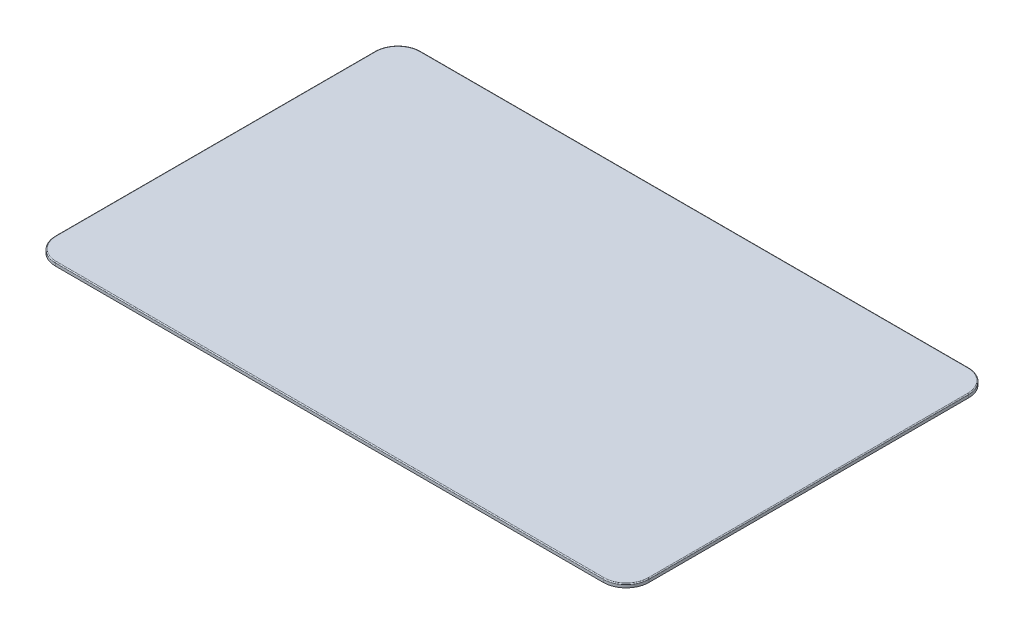
SolidWorks part; units mm, degrees
ref_plane "Спереди" through (0, 0, 0) normal (0, 0, 1) x (1, 0, 0)
ref_plane "Сверху" through (0, 0, 0) normal (0, 1, 0) x (1, 0, 0)
ref_plane "Справа" through (0, 0, 0) normal (1, 0, 0) x (0, 0, -1)
sketch "Эскиз1" plane through (0, 0, 0) normal (0, 1, 0) x (1, 0, 0)
  line L1 (-600, -400) -> (600, -400)
  line L2 (-650, -350) -> (-650, 350)
  line L3 (-600, 400) -> (600, 400)
  line L4 (650, -350) -> (650, 350)
  line L5 (-650, -400) -> (650, 400) construction
  line L6 (-650, 400) -> (650, -400) construction
  arc A0 (-600, 400) -> (-650, 350) centre (-600, 350) ccw
  arc A1 (600, 400) -> (650, 350) centre (600, 350) cw
  arc A2 (650, -350) -> (600, -400) centre (600, -350) cw
  arc A3 (-600, -400) -> (-650, -350) centre (-600, -350) cw
  point P0 (0, 0)
  dimension "D1" = 50
  dimension "D4" = 50
  dimension "D2" = 1300
  dimension "D3" = 800
extrude "Бобышка-Вытянуть1" add sketch "Эскиз1" along normal blind 8
fillet "Скругление1" radius 2 8 edges at (-635.3553, 8, -385.3553) (0, 8, -400) (635.3553, 8, -385.3553) (650, 8, 0) (635.3553, 8, 385.3553) (0, 8, 400) (-635.3553, 8, 385.3553) (-650, 8, 0)
sketch "Эскиз2" plane through (0, 0, 0) normal (0, -1, 0) x (1, 0, 0)
  line L0 (0, 398) -> (0, 197.3407) construction
  line L1 (-498, -35) -> (-405.9312, -35) construction
  line L2 (-494.82, 35) -> (-402.7512, 35) construction
  line L3 (-498, -100.1909) -> (-498, 80.8489) construction
  line L4 (-505.5, -118.7139) -> (-423, -118.7139)
  line L5 (-480.5, -93.7139) -> (-448, -93.7139)
  line L6 (-418, 113.7139) -> (-418, 29.5)
  line L7 (250, 398) -> (250, -398) construction
  line L8 (-250, 398) -> (-250, -398) construction
  line L9 (-648, 0) -> (648, 0) construction
  line L10 (302.5206, -212.9276) -> (307.7592, -212.906)
  line L11 (145, 35) -> (145, 50)
  line L12 (259.7408, -280.6043) -> (259.7408, -218.094)
  line L13 (262.2408, -283.1043) -> (308.0492, -283.1043)
  line L14 (265.5, -179.2861) -> (207.5, -179.2861)
  line L15 (-505.5, 118.7139) -> (-423, 118.7139)
  line L16 (-443, 88.7139) -> (-443, -88.7139)
  line L17 (-480.5, 93.7139) -> (-448, 93.7139)
  line L18 (-485.5, 84.9278) -> (-485.5, 88.7139)
  line L19 (-510.5, 85.0723) -> (-510.5, 113.7139)
  line L20 (-523.5388, 12.3957) -> (-523.2695, 77.6043)
  line L21 (403, -14.5) -> (302.5, -14.5)
  line L22 (403, 14.5) -> (302.5, 14.5)
  line L23 (418, -29.5) -> (418, -113.7139)
  line L24 (265.5, 174.2861) -> (207.5, 174.2861)
  line L25 (-515.5206, -80.0724) -> (-520.7592, -80.094)
  line L26 (22.5, -35) -> (-22.5, -35)
  line L27 (270.5, -174.2861) -> (270.5, 169.2861)
  line L28 (197.4794, 212.9276) -> (192.2408, 212.906)
  line L29 (240.2592, 280.6043) -> (240.2592, 218.125)
  line L30 (25, -32.5) -> (25, 35)
  line L31 (237.7592, 283.1043) -> (191.9508, 283.1043)
  line L32 (250, 213.1446) -> (245.2798, 213.1251)
  line L33 (310.5388, -280.6043) -> (310.2695, -215.3957)
  line L34 (-472.7408, -12.3957) -> (-472.7408, -77.3957)
  line L35 (297.5, -207.9277) -> (297.5, -19.5)
  line L36 (202.5, -207.9277) -> (202.5, -184.2861)
  line L37 (-475.2408, 79.906) -> (-480.5206, 79.9278)
  line L38 (-302.5206, 212.9276) -> (-307.7592, 212.906)
  line L39 (-265.5, 179.2861) -> (-207.5, 179.2861)
  line L40 (-259.7408, 280.6043) -> (-259.7408, 218.1043)
  line L41 (189.4612, -280.6043) -> (189.7305, -215.3957)
  line L42 (-262.2408, 283.1043) -> (-308.0492, 283.1043)
  line L43 (-254.7408, 213.1043) -> (-245.2592, 213.1043)
  line L44 (237.7592, -283.1043) -> (191.9508, -283.1043)
  line L45 (95, 100) -> (26, 100)
  line L46 (240.2592, -280.6043) -> (240.2592, -218.094)
  line L47 (197.4794, -212.9276) -> (192.2408, -212.906)
  line L48 (-25, -32.5) -> (-25, 35)
  line L50 (-310.5388, 280.6043) -> (-310.2695, 215.3957)
  line L51 (-297.5, 207.9277) -> (-297.5, 14.5)
  line L52 (-202.5, 207.9277) -> (-202.5, 184.2861)
  line L53 (-189.4612, 280.6043) -> (-189.7305, 215.3957)
  line L54 (-265.5, -174.2861) -> (-207.5, -174.2861)
  line L55 (-95, 100) -> (-23, 100)
  line L56 (-475.2408, -9.8957) -> (-521.0492, -9.8957)
  line L57 (-475.2408, -79.906) -> (-480.5206, -79.9278)
  line L58 (-475.2408, 9.8957) -> (-521.0492, 9.8957)
  line L59 (-523.5388, -12.3957) -> (-523.2695, -77.6043)
  line L60 (-510.5, -85.0723) -> (-510.5, -113.7139)
  line L61 (-472.7408, 12.3957) -> (-472.7408, 77.3957)
  line L62 (-515.5206, 80.0724) -> (-520.7592, 80.094)
  line L63 (-485.5, -84.9278) -> (-485.5, -88.7139)
  line L64 (-23, 147.3407) -> (-23.5, 147.3407)
  line L65 (-197.4794, -212.9276) -> (-192.2408, -212.906)
  line L66 (-240.2592, -280.6043) -> (-240.2592, -218.125)
  line L67 (82.5, -35) -> (37.5, -35)
  line L68 (-237.7592, -283.1043) -> (-191.9508, -283.1043)
  line L69 (-250, -213.1446) -> (-245.2798, -213.1251)
  line L70 (485.5, -84.9278) -> (485.5, -88.7139)
  line L71 (-189.4612, -280.6043) -> (-189.7305, -215.3957)
  line L72 (-202.5, -207.9277) -> (-202.5, -179.2861)
  line L73 (-297.5, -207.9277) -> (-297.5, -14.5)
  line L74 (515.5206, 80.0724) -> (520.7592, 80.094)
  line L75 (472.7408, 12.3957) -> (472.7408, 77.3957)
  line L76 (510.5, -85.0723) -> (510.5, -113.7139)
  line L77 (523.5388, -12.3957) -> (523.2695, -77.6043)
  line L78 (475.2408, 9.8957) -> (521.0492, 9.8957)
  line L79 (475.2408, -79.906) -> (480.5206, -79.9278)
  line L80 (475.2408, -9.8957) -> (521.0492, -9.8957)
  line L81 (85, -32.5) -> (85, 35)
  line L82 (35, -32.5) -> (35, 35)
  line L84 (-145, 35) -> (-145, 50)
  line L86 (142.5, -35) -> (97.5, -35)
  line L87 (145, -32.5) -> (145, 35)
  line L88 (95, -32.5) -> (95, 35)
  line L89 (21, 105) -> (21, 142.3407)
  line L90 (26.5, 149.8407) -> (26.5, 194.8407)
  line L91 (-18, 105) -> (-18, 142.3407)
  line L92 (-97.5, -35) -> (-142.5, -35)
  line L93 (-95, -32.5) -> (-95, 35)
  line L94 (-145, -32.5) -> (-145, 35)
  line L95 (24, 197.3407) -> (-21, 197.3407)
  line L96 (-23.5, 149.8407) -> (-23.5, 194.8407)
  line L98 (-37.5, -35) -> (-82.5, -35)
  line L99 (-35, -32.5) -> (-35, 35)
  line L100 (-85, -32.5) -> (-85, 35)
  line L105 (0, 147.3407) -> (0, 115.0711) construction
  line L108 (0, 0) -> (0, -400) construction
  line L112 (-310.5388, -280.6043) -> (-310.2695, -215.3957)
  line L114 (-237.7592, 283.1043) -> (-191.9508, 283.1043)
  line L116 (-240.2592, 280.6043) -> (-240.2592, 218.1043)
  line L117 (-197.4794, 212.9276) -> (-192.2408, 212.906)
  line L118 (-270.5, 174.2861) -> (-270.5, -169.2861)
  line L122 (-418, -29.5) -> (-418, -113.7139)
  line L123 (189.4612, 280.6043) -> (189.7305, 215.3957)
  line L124 (202.5, 207.9277) -> (202.5, 179.2861)
  line L125 (297.5, 207.9277) -> (297.5, 19.5)
  line L126 (310.5388, 280.6043) -> (310.2695, 215.3957)
  line L127 (250, 213.1446) -> (254.7202, 213.1251)
  line L128 (262.2408, 283.1043) -> (308.0492, 283.1043)
  line L129 (259.7408, 280.6043) -> (259.7408, 218.125)
  line L131 (302.5206, 212.9276) -> (307.7592, 212.906)
  line L132 (498, -100.1909) -> (498, 80.8489) construction
  line L133 (475.2408, 79.906) -> (480.5206, 79.9278)
  line L134 (472.7408, -12.3957) -> (472.7408, -77.3957)
  line L135 (515.5206, -80.0724) -> (520.7592, -80.094)
  line L136 (523.5388, 12.3957) -> (523.2695, 77.6043)
  line L137 (-403, 14.5) -> (-297.5, 14.5)
  line L138 (-403, -14.5) -> (-297.5, -14.5)
  line L139 (-250, -213.1446) -> (-254.7202, -213.1251)
  line L140 (510.5, 85.0723) -> (510.5, 113.7139)
  line L141 (485.5, 84.9278) -> (485.5, 88.7139)
  line L142 (-262.2408, -283.1043) -> (-308.0492, -283.1043)
  line L143 (494.82, 35) -> (402.7512, 35) construction
  line L144 (498, -35) -> (405.9312, -35) construction
  line L145 (480.5, 93.7139) -> (448, 93.7139)
  line L146 (443, 88.7139) -> (443, -88.7139)
  line L147 (505.5, 118.7139) -> (423, 118.7139)
  line L148 (418, 113.7139) -> (418, 29.5)
  line L149 (480.5, -93.7139) -> (448, -93.7139)
  line L150 (-259.7408, -280.6043) -> (-259.7408, -218.125)
  line L151 (505.5, -118.7139) -> (423, -118.7139)
  line L153 (-302.5206, -212.9276) -> (-307.7592, -212.906)
  line L160 (254.7408, -213.094) -> (245.2592, -213.094)
  arc A0 (240.2592, -218.094) -> (245.2592, -213.094) centre (245.2592, -218.094) cw
  arc A1 (297.5, -207.9277) -> (302.5206, -212.9276) centre (302.5, -207.9277) ccw
  arc A2 (310.2695, -215.3957) -> (307.7592, -212.906) centre (310.2592, -212.8957) ccw
  arc A3 (259.7408, 218.125) -> (254.7202, 213.1251) centre (254.7408, 218.125) cw
  arc A4 (245.2798, 213.1251) -> (240.2592, 218.125) centre (245.2592, 218.125) cw
  arc A5 (202.5, -184.2861) -> (207.5, -179.2861) centre (207.5, -184.2861) cw
  arc A6 (308.0492, -283.1043) -> (310.5388, -280.6043) centre (310.5492, -283.1043) ccw
  arc A7 (259.7408, -280.6043) -> (262.2408, -283.1043) centre (259.7408, -283.1043) ccw
  arc A8 (240.2592, -280.6043) -> (237.7592, -283.1043) centre (240.2592, -283.1043) cw
  arc A9 (191.9508, -283.1043) -> (189.4612, -280.6043) centre (189.4508, -283.1043) cw
  arc A10 (270.5, 169.2861) -> (265.5, 174.2861) centre (265.5, 169.2861) ccw
  arc A11 (510.5, 113.7139) -> (505.5, 118.7139) centre (505.5, 113.7139) ccw
  arc A12 (265.5, -179.2861) -> (270.5, -174.2861) centre (265.5, -174.2861) ccw
  arc A13 (189.7305, -215.3957) -> (192.2408, -212.906) centre (189.7408, -212.8957) cw
  arc A14 (202.5, -207.9277) -> (197.4794, -212.9276) centre (197.5, -207.9277) cw
  arc A15 (254.7408, -213.094) -> (259.7408, -218.094) centre (254.7408, -218.094) cw
  arc A16 (-240.2592, 218.1043) -> (-245.2592, 213.1043) centre (-245.2592, 218.1043) cw
  arc A17 (505.5, -118.7139) -> (510.5, -113.7139) centre (505.5, -113.7139) ccw
  arc A18 (-254.7408, 213.1043) -> (-259.7408, 218.1043) centre (-254.7408, 218.1043) cw
  arc A19 (-202.5, 184.2861) -> (-207.5, 179.2861) centre (-207.5, 184.2861) cw
  arc A20 (413, 24.5) -> (418, 29.5) centre (413, 29.5) ccw
  arc A21 (202.5, 207.9277) -> (197.4794, 212.9276) centre (197.5, 207.9277) ccw
  arc A22 (189.7305, 215.3957) -> (192.2408, 212.906) centre (189.7408, 212.8957) ccw
  arc A23 (403, 14.5) -> (408, 19.5) centre (403, 19.5) ccw
  arc A24 (191.9508, 283.1043) -> (189.4612, 280.6043) centre (189.4508, 283.1043) ccw
  arc A25 (240.2592, 280.6043) -> (237.7592, 283.1043) centre (240.2592, 283.1043) ccw
  arc A26 (259.7408, 280.6043) -> (262.2408, 283.1043) centre (259.7408, 283.1043) cw
  arc A27 (308.0492, 283.1043) -> (310.5388, 280.6043) centre (310.5492, 283.1043) cw
  arc A28 (413, 24.5) -> (408, 19.5) centre (413, 19.5) ccw
  arc A29 (310.2695, 215.3957) -> (307.7592, 212.906) centre (310.2592, 212.8957) cw
  arc A30 (297.5, 207.9277) -> (302.5206, 212.9276) centre (302.5, 207.9277) cw
  arc A31 (413, -24.5) -> (408, -19.5) centre (413, -19.5) cw
  arc A32 (202.5, 179.2861) -> (207.5, 174.2861) centre (207.5, 179.2861) ccw
  arc A33 (-270.5, -169.2861) -> (-265.5, -174.2861) centre (-265.5, -169.2861) ccw
  arc A34 (485.5, 88.7139) -> (480.5, 93.7139) centre (480.5, 88.7139) ccw
  arc A35 (-443, -88.7139) -> (-448, -93.7139) centre (-448, -88.7139) cw
  arc A36 (480.5206, 79.9278) -> (485.5, 84.9278) centre (480.5, 84.9278) ccw
  arc A37 (510.5, 85.0723) -> (515.5206, 80.0724) centre (515.5, 85.0723) ccw
  arc A38 (472.7408, -12.3957) -> (475.2408, -9.8957) centre (472.7408, -9.8957) cw
  arc A39 (521.0492, -9.8957) -> (523.5388, -12.3957) centre (523.5492, -9.8957) cw
  arc A40 (475.2408, -79.906) -> (472.7408, -77.3957) centre (472.7408, -79.8957) cw
  arc A41 (523.2695, -77.6043) -> (520.7592, -80.094) centre (523.2592, -80.1043) cw
  arc A42 (510.5, -85.0723) -> (515.5206, -80.0724) centre (515.5, -85.0723) cw
  arc A43 (480.5206, -79.9278) -> (485.5, -84.9278) centre (480.5, -84.9278) cw
  arc A44 (523.2695, 77.6043) -> (520.7592, 80.094) centre (523.2592, 80.1043) ccw
  arc A45 (-418, -113.7139) -> (-423, -118.7139) centre (-423, -113.7139) cw
  arc A46 (485.5, -88.7139) -> (480.5, -93.7139) centre (480.5, -88.7139) cw
  arc A47 (475.2408, 79.906) -> (472.7408, 77.3957) centre (472.7408, 79.8957) ccw
  arc A48 (521.0492, 9.8957) -> (523.5388, 12.3957) centre (523.5492, 9.8957) ccw
  arc A49 (472.7408, 12.3957) -> (475.2408, 9.8957) centre (472.7408, 9.8957) ccw
  arc A50 (-443, 88.7139) -> (-448, 93.7139) centre (-448, 88.7139) ccw
  arc A51 (-418, 113.7139) -> (-423, 118.7139) centre (-423, 113.7139) ccw
  arc A52 (418, 113.7139) -> (423, 118.7139) centre (423, 113.7139) cw
  arc A53 (443, 88.7139) -> (448, 93.7139) centre (448, 88.7139) cw
  arc A54 (418, -113.7139) -> (423, -118.7139) centre (423, -113.7139) ccw
  arc A55 (443, -88.7139) -> (448, -93.7139) centre (448, -88.7139) ccw
  arc A56 (-472.7408, 12.3957) -> (-475.2408, 9.8957) centre (-472.7408, 9.8957) cw
  arc A57 (-521.0492, 9.8957) -> (-523.5388, 12.3957) centre (-523.5492, 9.8957) cw
  arc A58 (-475.2408, 79.906) -> (-472.7408, 77.3957) centre (-472.7408, 79.8957) cw
  arc A59 (-485.5, -88.7139) -> (-480.5, -93.7139) centre (-480.5, -88.7139) ccw
  arc A60 (-523.2695, 77.6043) -> (-520.7592, 80.094) centre (-523.2592, 80.1043) cw
  arc A61 (-480.5206, -79.9278) -> (-485.5, -84.9278) centre (-480.5, -84.9278) ccw
  arc A62 (-510.5, -85.0723) -> (-515.5206, -80.0724) centre (-515.5, -85.0723) ccw
  arc A63 (-523.2695, -77.6043) -> (-520.7592, -80.094) centre (-523.2592, -80.1043) ccw
  arc A64 (-475.2408, -79.906) -> (-472.7408, -77.3957) centre (-472.7408, -79.8957) ccw
  arc A65 (-521.0492, -9.8957) -> (-523.5388, -12.3957) centre (-523.5492, -9.8957) ccw
  arc A66 (-472.7408, -12.3957) -> (-475.2408, -9.8957) centre (-472.7408, -9.8957) ccw
  arc A67 (-510.5, 85.0723) -> (-515.5206, 80.0724) centre (-515.5, 85.0723) cw
  arc A68 (-480.5206, 79.9278) -> (-485.5, 84.9278) centre (-480.5, 84.9278) cw
  arc A69 (-485.5, 88.7139) -> (-480.5, 93.7139) centre (-480.5, 88.7139) cw
  arc A70 (-202.5, -179.2861) -> (-207.5, -174.2861) centre (-207.5, -179.2861) ccw
  arc A71 (-270.5, 174.2861) -> (-265.5, 179.2861) centre (-265.5, 174.2861) cw
  arc A72 (297.5, 19.5) -> (302.5, 14.5) centre (302.5, 19.5) ccw
  arc A73 (-297.5, 207.9277) -> (-302.5206, 212.9276) centre (-302.5, 207.9277) ccw
  arc A74 (-310.2695, 215.3957) -> (-307.7592, 212.906) centre (-310.2592, 212.8957) ccw
  arc A75 (297.5, -19.5) -> (302.5, -14.5) centre (302.5, -19.5) cw
  arc A76 (-308.0492, 283.1043) -> (-310.5388, 280.6043) centre (-310.5492, 283.1043) ccw
  arc A77 (-259.7408, 280.6043) -> (-262.2408, 283.1043) centre (-259.7408, 283.1043) ccw
  arc A78 (-240.2592, 280.6043) -> (-237.7592, 283.1043) centre (-240.2592, 283.1043) cw
  arc A79 (-191.9508, 283.1043) -> (-189.4612, 280.6043) centre (-189.4508, 283.1043) cw
  arc A80 (-418, -29.5) -> (-413, -24.5) centre (-413, -29.5) cw
  arc A81 (-189.7305, 215.3957) -> (-192.2408, 212.906) centre (-189.7408, 212.8957) cw
  arc A82 (-202.5, 207.9277) -> (-197.4794, 212.9276) centre (-197.5, 207.9277) cw
  arc A83 (-403, -14.5) -> (-408, -19.5) centre (-403, -19.5) ccw
  arc A84 (-240.2592, -218.125) -> (-245.2798, -213.1251) centre (-245.2592, -218.125) ccw
  arc A85 (-254.7202, -213.1251) -> (-259.7408, -218.125) centre (-254.7408, -218.125) ccw
  arc A86 (-505.5, -118.7139) -> (-510.5, -113.7139) centre (-505.5, -113.7139) cw
  arc A87 (403, -14.5) -> (408, -19.5) centre (403, -19.5) cw
  arc A88 (413, -24.5) -> (418, -29.5) centre (413, -29.5) cw
  arc A89 (-202.5, -207.9277) -> (-197.4794, -212.9276) centre (-197.5, -207.9277) ccw
  arc A90 (-189.7305, -215.3957) -> (-192.2408, -212.906) centre (-189.7408, -212.8957) ccw
  arc A91 (-418, 29.5) -> (-413, 24.5) centre (-413, 29.5) ccw
  arc A92 (-510.5, 113.7139) -> (-505.5, 118.7139) centre (-505.5, 113.7139) cw
  arc A93 (-403, 14.5) -> (-408, 19.5) centre (-403, 19.5) cw
  arc A94 (-191.9508, -283.1043) -> (-189.4612, -280.6043) centre (-189.4508, -283.1043) ccw
  arc A95 (-240.2592, -280.6043) -> (-237.7592, -283.1043) centre (-240.2592, -283.1043) ccw
  arc A96 (-259.7408, -280.6043) -> (-262.2408, -283.1043) centre (-259.7408, -283.1043) cw
  arc A97 (-308.0492, -283.1043) -> (-310.5388, -280.6043) centre (-310.5492, -283.1043) cw
  arc A98 (-408, 19.5) -> (-413, 24.5) centre (-413, 19.5) ccw
  arc A99 (-413, -24.5) -> (-408, -19.5) centre (-413, -19.5) ccw
  arc A100 (22.5, -35) -> (25, -32.5) centre (25, -35) ccw
  arc A101 (-310.2695, -215.3957) -> (-307.7592, -212.906) centre (-310.2592, -212.8957) cw
  arc A102 (-297.5, -207.9277) -> (-302.5206, -212.9276) centre (-302.5, -207.9277) cw
  arc A103 (-25, -32.5) -> (-22.5, -35) centre (-25, -35) ccw
  arc A104 (-37.5, -35) -> (-35, -32.5) centre (-35, -35) ccw
  arc A105 (-85, -32.5) -> (-82.5, -35) centre (-85, -35) ccw
  arc A106 (-97.5, -35) -> (-95, -32.5) centre (-95, -35) ccw
  arc A107 (-145, -32.5) -> (-142.5, -35) centre (-145, -35) ccw
  arc A108 (35, -32.5) -> (37.5, -35) centre (35, -35) ccw
  arc A109 (82.5, -35) -> (85, -32.5) centre (85, -35) ccw
  arc A110 (95, -32.5) -> (97.5, -35) centre (95, -35) ccw
  arc A111 (142.5, -35) -> (145, -32.5) centre (145, -35) ccw
  arc A112 (35, 35) -> (25, 35) centre (30, 35) ccw
  arc A113 (95, 35) -> (85, 35) centre (90, 35) ccw
  arc A114 (-25, 35) -> (-35, 35) centre (-30, 35) ccw
  arc A115 (-85, 35) -> (-95, 35) centre (-90, 35) ccw
  arc A116 (-23, 100) -> (-18, 105) centre (-23, 105) ccw
  arc A117 (21, 105) -> (26, 100) centre (26, 105) ccw
  arc A120 (-145, 50) -> (-95, 100) centre (-95, 50) cw
  arc A121 (145, 50) -> (95, 100) centre (95, 50) ccw
  arc A122 (-21.0327, 146.9374) -> (-18, 142.3407) centre (-23, 142.3407) cw
  arc A123 (24.0327, 146.9374) -> (21, 142.3407) centre (26, 142.3407) ccw
  arc A124 (24.0327, 146.9374) -> (26.5, 149.8407) centre (26.5, 147.3407) ccw
  arc A125 (-23.5, 149.8407) -> (-21.0327, 146.9374) centre (-23.5, 147.3407) ccw
  arc A126 (26.5, 194.8407) -> (24, 197.3407) centre (26.5, 197.3407) ccw
  arc A127 (-21, 197.3407) -> (-23.5, 194.8407) centre (-23.5, 197.3407) ccw
  point P24 (285, -248)
  point P39 (285, -213)
  point P75 (202.5, -179.2861)
  point P139 (215, -213)
  point P140 (215, -248)
  point P141 (250, -186.7861)
  point P142 (250, -186.7861)
  point P144 (-240.2592, 213.1043)
  point P148 (-259.7408, 213.1043)
  point P199 (250, 186.7861)
  point P200 (215, 248)
  point P201 (215, 213)
  point P202 (285, 213)
  point P203 (285, 248)
  point P241 (498, -80)
  point P242 (498, -45)
  point P243 (463, -106.2139)
  point P244 (463, -106.2139)
  point P267 (-202.5, 179.2861)
  point P268 (463, 106.2139)
  point P269 (498, 45)
  point P270 (498, 80)
  point P384 (-498, 80)
  point P385 (-498, 45)
  point P388 (-463, 106.2139)
  point P389 (-463, -106.2139)
  point P390 (-498, -45)
  point P391 (-498, -80)
  point P392 (-285, 248)
  point P393 (-285, 213)
  point P394 (-215, 213)
  point P395 (-215, 248)
  point P396 (-250, 186.7861)
  point P397 (-250, -186.7861)
  point P398 (-215, -248)
  point P399 (-215, -213)
  point P400 (-285, -213)
  point P401 (-285, -248)
  dimension "D2" = 5
  dimension "D3" = 5
  dimension "D4" = 5
  dimension "D6" = 5
  dimension "D7" = 50
  dimension "D15" = 5
  dimension "D16" = 5
  dimension "D17" = 5
  dimension "D18" = 5
  dimension "D19" = 5
  dimension "D20" = 5
  dimension "D5" = 5
  dimension "D21" = 5
  dimension "D22" = 5
  dimension "D23" = 5
  dimension "D24" = 5
  dimension "D25" = 5
extrude "Вырез-Вытянуть1" cut sketch "Эскиз2" against normal blind 6 contours L95 A127 L96 A125 A122 L91 A116 L55 A120 L84 L94 A107 L92 A106 L93 A115 L100 A105 L98 A104 L99 A114 L48 A103 L26 A100 L30 A112 L82 A108 L67 A109 L81 A113 L88 A110 L86 A111 L87 L11 A121 L45 A117 L89 A123 A124 L90 A126 | A31 A88 L23 A54 L151 A17 L76 A42 L135 A41 L77 A39 L80 A38 L134 A40 L79 A43 L70 A46 L149 A55 L146 A53 L145 A34 L141 A36 L133 A47 L75 A49 L78 A48 L136 A44 L74 A37 L140 A11 L147 A52 L148 A20 A28 A23 L22 A72 L125 A30 L131 | L51 L137 A93 A98 A91 L6 A51 L15 A92 L19 A67 L62 A60 L20 A57 L58 A56 L61 A58 L37 A68 L18 A69 L17 A50 L16 A35 L5 A59 L63 A61 L57 A64 L34 A66 L56 A65 L59 A63 L25 A62 L60 A86 L4 A45 L122 A80 A99 A83 L138 L73 A102 L153 A101 L112 A97 L142 A96 L150 A85 L139 L69 A84 L66 A95 L68 A94 L71 A90 L65 A89 L72 A70 L54 A33 L118 A71 L39 A19 L52 A82 L117 A81 L53 A79 L114 A78 L116 A16 L43 A18 L40 A77 L42 A76 L50 A74 L38 A73 region at (337.62, 0, 1.1629) region at (0.1673, 0, 46.3033)
